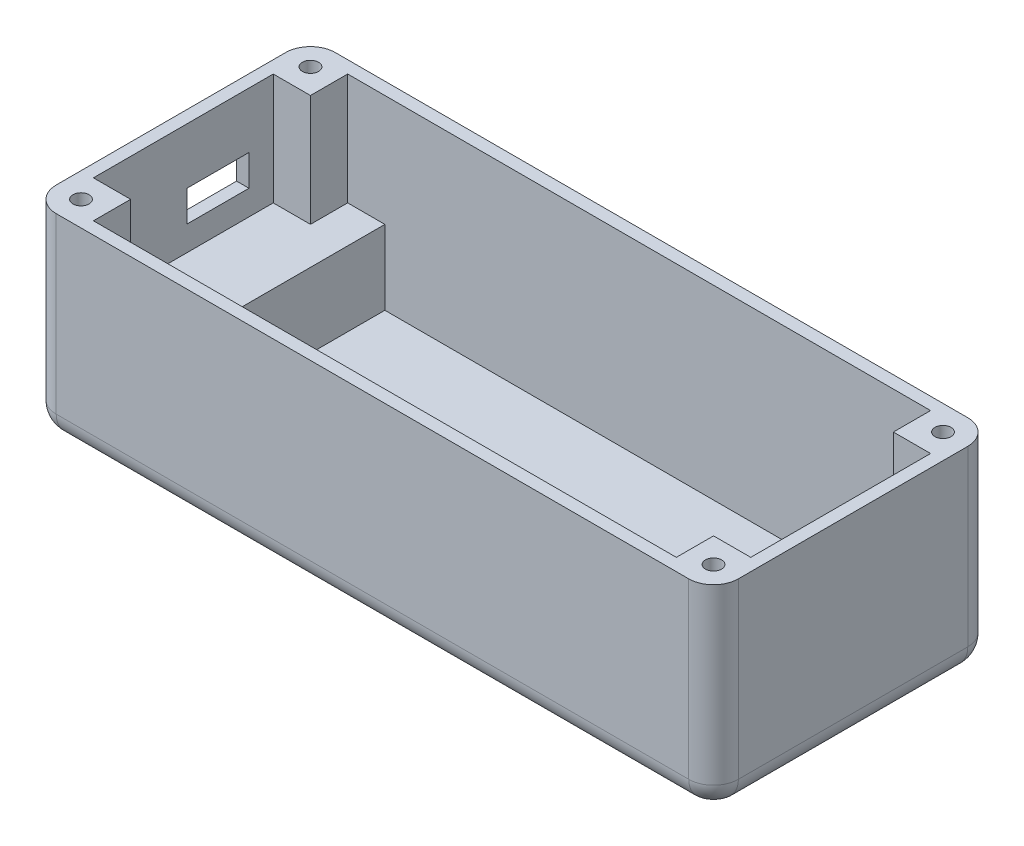
SolidWorks part; units mm, degrees
ref_plane "Front Plane" through (0, 0, 0) normal (0, 0, 1) x (1, 0, 0)
ref_plane "Top Plane" through (0, 0, 0) normal (0, 1, 0) x (1, 0, 0)
ref_plane "Right Plane" through (0, 0, 0) normal (1, 0, 0) x (0, 0, -1)
sketch "Sketch1" plane through (0, 0, 0) normal (0, 1, 0) x (1, 0, 0)
  line L1 (-55, 22.5) -> (55, 22.5)
  line L2 (-55, 22.5) -> (-55, -22.5)
  line L3 (-55, -22.5) -> (55, -22.5)
  line L4 (55, 22.5) -> (55, -22.5)
  line L5 (-55, 22.5) -> (55, -22.5) construction
  line L6 (-55, -22.5) -> (55, 22.5) construction
  point P0 (0, 0)
  dimension "D1" = 45
  dimension "D2" = 110
extrude "Boss-Extrude1" add sketch "Sketch1" along normal blind 2
sketch "Sketch3" plane through (0, 2, 0) normal (0, 1, 0) x (1, 0, 0)
  line L1 (-55, 22.5) -> (55, 22.5)
  line L2 (-55, 22.5) -> (-55, -22.5)
  line L3 (-55, -22.5) -> (55, -22.5)
  line L4 (55, 22.5) -> (55, -22.5)
  line L5 (-55, 22.5) -> (55, -22.5) construction
  line L6 (-55, -22.5) -> (55, 22.5) construction
  line L7 (-53, 20.5) -> (53, 20.5)
  line L8 (-53, 20.5) -> (-53, -20.5)
  line L9 (-53, -20.5) -> (53, -20.5)
  line L10 (53, 20.5) -> (53, -20.5)
  line L11 (-53, 20.5) -> (53, -20.5) construction
  line L12 (-53, -20.5) -> (53, 20.5) construction
  point P0 (0, 0)
  point P7 (0, 0)
  dimension "D1" = 41
  dimension "D2" = 106
extrude "Boss-Extrude2" add sketch "Sketch3" along normal blind 30
sketch "Sketch4" plane through (0, 2, 0) normal (0, 1, 0) x (1, 0, 0)
  line L0 (-53, -20.5) -> (53, -20.5) construction
  line L1 (-53, 20.5) -> (-41, 20.5)
  line L2 (-53, 20.5) -> (-53, -20.5)
  line L3 (-53, -20.5) -> (-41, -20.5)
  line L4 (-41, 20.5) -> (-41, -20.5)
  line L5 (-53, -20.5) -> (53, -20.5) construction
  line L6 (53, 20.5) -> (41, 20.5)
  line L7 (53, 20.5) -> (53, -20.5)
  line L8 (53, -20.5) -> (41, -20.5)
  line L9 (41, 20.5) -> (41, -20.5)
  dimension "D1" = 12
  dimension "D2" = 12
extrude "Boss-Extrude3" add sketch "Sketch4" along normal blind 12
sketch "Sketch5" plane through (0, 14, 0) normal (0, 1, 0) x (1, 0, 0)
  line L1 (-53, 20.5) -> (-47, 20.5)
  line L2 (-53, 20.5) -> (-53, 14.5)
  line L3 (-53, 14.5) -> (-47, 14.5)
  line L4 (-47, 20.5) -> (-47, 14.5)
  line L5 (-53, -20.5) -> (-47, -20.5)
  line L6 (-53, -20.5) -> (-53, -14.5)
  line L7 (-53, -14.5) -> (-47, -14.5)
  line L8 (-47, -20.5) -> (-47, -14.5)
  dimension "D1" = 6
  dimension "D2" = 6
  dimension "D3" = 6
  dimension "D4" = 6
extrude "Boss-Extrude4" add sketch "Sketch5" along normal blind 18
sketch "Sketch6" plane through (0, 14, 0) normal (0, 1, 0) x (1, 0, 0)
  line L1 (53, 20.5) -> (47, 20.5)
  line L2 (53, 20.5) -> (53, 14.5)
  line L3 (53, 14.5) -> (47, 14.5)
  line L4 (47, 20.5) -> (47, 14.5)
  line L5 (53, -20.5) -> (47, -20.5)
  line L6 (53, -20.5) -> (53, -14.5)
  line L7 (53, -14.5) -> (47, -14.5)
  line L8 (47, -20.5) -> (47, -14.5)
  dimension "D1" = 6
  dimension "D2" = 6
  dimension "D3" = 6
  dimension "D4" = 6
extrude "Boss-Extrude5" add sketch "Sketch6" along normal blind 18
fillet "Fillet1" radius 4 4 edges at (55, 16, -22.5) (55, 16, 22.5) (-55, 16, 22.5) (-55, 16, -22.5)
fillet "Fillet2" radius 4 8 edges at (53.8284, 0, 21.3284) (53.8284, 0, -21.3284) (55, 0, 0) (-53.8284, 0, 21.3284) (0, 0, 22.5) (-53.8284, 0, -21.3284) (-55, 0, 0) (0, 0, -22.5)
sketch "Sketch7" plane through (0, 32, 0) normal (0, 1, 0) x (1, 0, 0)
  circle A0 centre (-51, 18.5) radius 1.3
  circle A1 centre (51, 18.5) radius 1.3
  circle A2 centre (51, -18.5) radius 1.3
  circle A3 centre (-51, -18.5) radius 1.3
  dimension "D1" = 2.6
  dimension "D2" = 2.6
  dimension "D3" = 2.6
  dimension "D4" = 2.6
extrude "Cut-Extrude1" cut sketch "Sketch7" against normal blind 34
sketch "Sketch8" plane through (0, 0, 0) normal (0, -1, 0) x (1, 0, 0)
  circle A0 centre (-51, 18.5) radius 2.9
  circle A1 centre (-51, -18.5) radius 2.9
  circle A2 centre (51, -18.5) radius 2.9
  circle A3 centre (51, 18.5) radius 2.9
  dimension "D1" = 5.8
  dimension "D2" = 5.8
  dimension "D3" = 5.8
  dimension "D4" = 5.8
extrude "Cut-Extrude2" cut sketch "Sketch8" against normal blind 25
sketch "Sketch9" plane through (0, 2, 0) normal (0, 1, 0) x (1, 0, 0)
  line L1 (41, 20.5) -> (41, -20.5) construction
  line L2 (31, 10) -> (41, 10)
  line L3 (31, 10) -> (31, -10)
  line L4 (31, -10) -> (41, -10)
  line L5 (41, 10) -> (41, -10)
  line L6 (31, 10) -> (41, -10) construction
  line L7 (31, -10) -> (41, 10) construction
  line L8 (41, 20.5) -> (-41, 20.5) construction
  point P2 (36, 0)
  dimension "D1" = 20
  dimension "D2" = 10
  dimension "D3" = 0
  dimension "D4" = 10.5
extrude "Cut-Extrude3" cut sketch "Sketch9" against normal blind 10
sketch "Sketch10" plane through (-53, 0, 0) normal (1, 0, 0) x (0, 0, -1)
  line L0 (14.5, 14) -> (-14.5, 14) construction
  line L1 (10.5859, 23) -> (0.5859, 23)
  line L2 (10.5859, 23) -> (10.5859, 18)
  line L3 (10.5859, 18) -> (0.5859, 18)
  line L4 (0.5859, 23) -> (0.5859, 18)
  line L5 (10.5859, 23) -> (0.5859, 18) construction
  line L6 (10.5859, 18) -> (0.5859, 23) construction
  point P0 (5.5859, 20.5)
  dimension "D1" = 10
  dimension "D2" = 5
  dimension "D3" = 4
extrude "Cut-Extrude4" cut sketch "Sketch10" against normal blind 10
